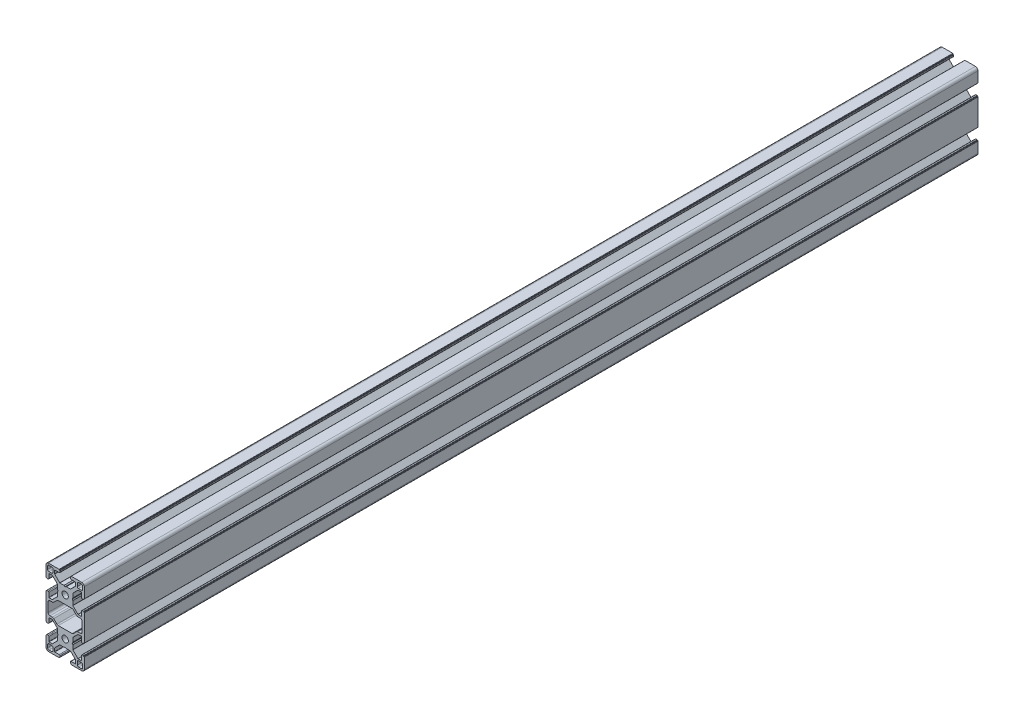
SolidWorks part; units mm, degrees
material "1060 Alloy"
ref_plane "Front" through (0, 0, 0) normal (0, 0, 1) x (1, 0, 0)
ref_plane "Top" through (0, 0, 0) normal (0, 1, 0) x (1, 0, 0)
ref_plane "Right" through (0, 0, 0) normal (1, 0, 0) x (0, 0, -1)
ref_plane "Plane1" through (0, 0, 25) normal (0, 0, 1) x (1, 0, 0)
sketch "Sketch1" plane through (0, 0, 25) normal (0, 0, 1) x (1, 0, 0)
  line L0 (-9.5, 12.7) -> (-9.5, 10.5)
  line L1 (-10.5, 9.5) -> (-12.7, 9.5)
  line L2 (-13.7, 10.5) -> (-13.7, 12.7)
  line L3 (-12.7, 13.7) -> (-10.5, 13.7)
  line L4 (12.7, 9.5) -> (10.5, 9.5)
  line L5 (9.5, 10.5) -> (9.5, 12.7)
  line L6 (10.5, 13.7) -> (12.7, 13.7)
  line L7 (13.7, 12.7) -> (13.7, 10.5)
  line L8 (-12.7, -39.5) -> (-10.5, -39.5)
  line L9 (-9.5, -40.5) -> (-9.5, -42.7)
  line L10 (-10.5, -43.7) -> (-12.7, -43.7)
  line L11 (-13.7, -42.7) -> (-13.7, -40.5)
  line L12 (9.5, -42.7) -> (9.5, -40.5)
  line L13 (10.5, -39.5) -> (12.7, -39.5)
  line L14 (13.7, -40.5) -> (13.7, -42.7)
  line L15 (12.7, -43.7) -> (10.5, -43.7)
  line L16 (0, 0) -> (0, -30) construction
  line L32 (8.9272, -20.5393) -> (6.4104, -23.0562)
  line L33 (5.3497, -23.4955) -> (-5.3497, -23.4955)
  line L34 (-6.4104, -23.0562) -> (-8.9272, -20.5393)
  line L35 (-9.9879, -20.1) -> (-11.85, -20.1)
  line L36 (-13.35, -18.6) -> (-13.35, -11.4)
  line L37 (-11.85, -9.9) -> (-9.9879, -9.9)
  line L38 (-8.9272, -9.4607) -> (-6.4104, -6.9438)
  line L39 (-5.3497, -6.5045) -> (5.3497, -6.5045)
  line L40 (6.4104, -6.9438) -> (8.9272, -9.4607)
  line L41 (9.9879, -9.9) -> (11.85, -9.9)
  line L42 (13.35, -11.4) -> (13.35, -18.6)
  line L43 (11.85, -20.1) -> (9.9879, -20.1)
  line L44 (13.4, -25.95) -> (14.3, -25.95)
  line L45 (14.5, -25.75) -> (14.5, -25.65)
  line L46 (14.7, -25.45) -> (14.8, -25.45)
  line L47 (15, -25.25) -> (15, -4.75)
  line L48 (14.8, -4.55) -> (14.7, -4.55)
  line L49 (14.5, -4.35) -> (14.5, -4.25)
  line L50 (14.3, -4.05) -> (13.4, -4.05)
  line L51 (12.8, -4.65) -> (12.8, -8.05)
  line L52 (12.6, -8.25) -> (10.1328, -8.25)
  line L53 (9.9914, -8.1914) -> (6.063, -4.263)
  line L54 (6.0045, -4.1216) -> (6.0045, -0.9)
  line L55 (6.0045, -0.9) -> (5.5426, -0.1)
  line L56 (5.5426, 0.1) -> (6.0045, 0.9)
  line L57 (6.0045, 0.9) -> (6.0045, 4.1216)
  line L58 (6.063, 4.263) -> (9.9914, 8.1914)
  line L59 (10.1328, 8.25) -> (12.6, 8.25)
  line L60 (12.8, 8.05) -> (12.8, 4.65)
  line L61 (13.4, 4.05) -> (14.3, 4.05)
  line L62 (14.5, 4.25) -> (14.5, 4.35)
  line L63 (14.7, 4.55) -> (14.8, 4.55)
  line L64 (15, 4.75) -> (15, 13)
  line L65 (13, 15) -> (4.75, 15)
  line L66 (4.55, 14.8) -> (4.55, 14.7)
  line L67 (4.35, 14.5) -> (4.25, 14.5)
  line L68 (4.05, 14.3) -> (4.05, 13.4)
  line L69 (4.65, 12.8) -> (8.05, 12.8)
  line L70 (8.25, 12.6) -> (8.25, 10.1328)
  line L71 (8.1914, 9.9914) -> (4.2586, 6.0586)
  line L72 (4.1172, 6) -> (0.9, 6)
  line L73 (0.9, 6) -> (0.1019, 5.5392)
  line L74 (-0.1019, 5.5392) -> (-0.9, 6)
  line L75 (-0.9, 6) -> (-4.1172, 6)
  line L76 (-4.2586, 6.0586) -> (-8.1914, 9.9914)
  line L77 (-8.25, 10.1328) -> (-8.25, 12.6)
  line L78 (-8.05, 12.8) -> (-4.65, 12.8)
  line L79 (-4.05, 13.4) -> (-4.05, 14.3)
  line L80 (-4.25, 14.5) -> (-4.35, 14.5)
  line L81 (-4.55, 14.7) -> (-4.55, 14.8)
  line L82 (-4.75, 15) -> (-13, 15)
  line L83 (-15, 13) -> (-15, 4.75)
  line L84 (-14.8, 4.55) -> (-14.7, 4.55)
  line L85 (-14.5, 4.35) -> (-14.5, 4.25)
  line L86 (-14.3, 4.05) -> (-13.4, 4.05)
  line L87 (-12.8, 4.65) -> (-12.8, 8.05)
  line L88 (-12.6, 8.25) -> (-10.1328, 8.25)
  line L89 (-9.9914, 8.1914) -> (-6.063, 4.263)
  line L90 (-6.0045, 4.1216) -> (-6.0045, 0.9)
  line L91 (-6.0045, 0.9) -> (-5.5426, 0.1)
  line L92 (-5.5426, -0.1) -> (-6.0045, -0.9)
  line L93 (-6.0045, -0.9) -> (-6.0045, -4.1216)
  line L94 (-6.063, -4.263) -> (-9.9914, -8.1914)
  line L95 (-10.1328, -8.25) -> (-12.6, -8.25)
  line L96 (-12.8, -8.05) -> (-12.8, -4.65)
  line L97 (-13.4, -4.05) -> (-14.3, -4.05)
  line L98 (-14.5, -4.25) -> (-14.5, -4.35)
  line L99 (-14.7, -4.55) -> (-14.8, -4.55)
  line L100 (-15, -4.75) -> (-15, -25.25)
  line L101 (-14.8, -25.45) -> (-14.7, -25.45)
  line L102 (-14.5, -25.65) -> (-14.5, -25.75)
  line L103 (-14.3, -25.95) -> (-13.4, -25.95)
  line L104 (-12.8, -25.35) -> (-12.8, -21.95)
  line L105 (-12.6, -21.75) -> (-10.1328, -21.75)
  line L106 (-9.9914, -21.8086) -> (-6.063, -25.737)
  line L107 (-6.0045, -25.8784) -> (-6.0045, -29.1)
  line L108 (-6.0045, -29.1) -> (-5.5426, -29.9)
  line L109 (-5.5426, -30.1) -> (-6.0045, -30.9)
  line L110 (-6.0045, -30.9) -> (-6.0045, -34.1216)
  line L111 (-6.063, -34.263) -> (-9.9914, -38.1914)
  line L112 (-10.1328, -38.25) -> (-12.6, -38.25)
  line L113 (-12.8, -38.05) -> (-12.8, -34.65)
  line L114 (-13.4, -34.05) -> (-14.3, -34.05)
  line L115 (-14.5, -34.25) -> (-14.5, -34.35)
  line L116 (-14.7, -34.55) -> (-14.8, -34.55)
  line L117 (-15, -34.75) -> (-15, -43)
  line L118 (-13, -45) -> (-4.75, -45)
  line L119 (-4.55, -44.8) -> (-4.55, -44.7)
  line L120 (-4.35, -44.5) -> (-4.25, -44.5)
  line L121 (-4.05, -44.3) -> (-4.05, -43.4)
  line L122 (-4.65, -42.8) -> (-8.05, -42.8)
  line L123 (-8.25, -42.6) -> (-8.25, -40.1328)
  line L124 (-8.1914, -39.9914) -> (-4.2586, -36.0586)
  line L125 (-4.1172, -36) -> (-0.9, -36)
  line L126 (-0.9, -36) -> (-0.1019, -35.5392)
  line L127 (0.1019, -35.5392) -> (0.9, -36)
  line L128 (0.9, -36) -> (4.1172, -36)
  line L129 (4.2586, -36.0586) -> (8.1914, -39.9914)
  line L130 (8.25, -40.1328) -> (8.25, -42.6)
  line L131 (8.05, -42.8) -> (4.65, -42.8)
  line L132 (4.05, -43.4) -> (4.05, -44.3)
  line L133 (4.25, -44.5) -> (4.35, -44.5)
  line L134 (4.55, -44.7) -> (4.55, -44.8)
  line L135 (4.75, -45) -> (13, -45)
  line L136 (15, -43) -> (15, -34.75)
  line L137 (14.8, -34.55) -> (14.7, -34.55)
  line L138 (14.5, -34.35) -> (14.5, -34.25)
  line L139 (14.3, -34.05) -> (13.4, -34.05)
  line L140 (12.8, -34.65) -> (12.8, -38.05)
  line L141 (12.6, -38.25) -> (10.1328, -38.25)
  line L142 (9.9914, -38.1914) -> (6.063, -34.263)
  line L143 (6.0045, -34.1216) -> (6.0045, -30.9)
  line L144 (6.0045, -30.9) -> (5.5426, -30.1)
  line L145 (5.5426, -29.9) -> (6.0045, -29.1)
  line L146 (6.0045, -29.1) -> (6.0045, -25.8784)
  line L147 (6.063, -25.737) -> (9.9914, -21.8086)
  line L148 (10.1328, -21.75) -> (12.6, -21.75)
  line L149 (12.8, -21.95) -> (12.8, -25.35)
  arc A0 (-9.5, 10.5) -> (-10.5, 9.5) centre (-10.5, 10.5) cw
  arc A1 (-12.7, 9.5) -> (-13.7, 10.5) centre (-12.7, 10.5) cw
  arc A2 (-13.7, 12.7) -> (-12.7, 13.7) centre (-12.7, 12.7) cw
  arc A3 (-10.5, 13.7) -> (-9.5, 12.7) centre (-10.5, 12.7) cw
  arc A4 (10.5, 9.5) -> (9.5, 10.5) centre (10.5, 10.5) cw
  arc A5 (9.5, 12.7) -> (10.5, 13.7) centre (10.5, 12.7) cw
  arc A6 (12.7, 13.7) -> (13.7, 12.7) centre (12.7, 12.7) cw
  arc A7 (13.7, 10.5) -> (12.7, 9.5) centre (12.7, 10.5) cw
  arc A8 (-10.5, -39.5) -> (-9.5, -40.5) centre (-10.5, -40.5) cw
  arc A9 (-9.5, -42.7) -> (-10.5, -43.7) centre (-10.5, -42.7) cw
  arc A10 (-12.7, -43.7) -> (-13.7, -42.7) centre (-12.7, -42.7) cw
  arc A11 (-13.7, -40.5) -> (-12.7, -39.5) centre (-12.7, -40.5) cw
  arc A12 (9.5, -40.5) -> (10.5, -39.5) centre (10.5, -40.5) cw
  arc A13 (12.7, -39.5) -> (13.7, -40.5) centre (12.7, -40.5) cw
  arc A14 (13.7, -42.7) -> (12.7, -43.7) centre (12.7, -42.7) cw
  arc A15 (10.5, -43.7) -> (9.5, -42.7) centre (10.5, -42.7) cw
  circle A16 centre (0, 0) radius 2.45
  circle A17 centre (0, -30) radius 2.45
  arc A32 (6.4104, -23.0562) -> (5.3497, -23.4955) centre (5.3497, -21.9955) cw
  arc A33 (-5.3497, -23.4955) -> (-6.4104, -23.0562) centre (-5.3497, -21.9955) cw
  arc A34 (-8.9272, -20.5393) -> (-9.9879, -20.1) centre (-9.9879, -21.6) ccw
  arc A35 (-11.85, -20.1) -> (-13.35, -18.6) centre (-11.85, -18.6) cw
  arc A36 (-13.35, -11.4) -> (-11.85, -9.9) centre (-11.85, -11.4) cw
  arc A37 (-9.9879, -9.9) -> (-8.9272, -9.4607) centre (-9.9879, -8.4) ccw
  arc A38 (-6.4104, -6.9438) -> (-5.3497, -6.5045) centre (-5.3497, -8.0045) cw
  arc A39 (5.3497, -6.5045) -> (6.4104, -6.9438) centre (5.3497, -8.0045) cw
  arc A40 (8.9272, -9.4607) -> (9.9879, -9.9) centre (9.9879, -8.4) ccw
  arc A41 (11.85, -9.9) -> (13.35, -11.4) centre (11.85, -11.4) cw
  arc A42 (13.35, -18.6) -> (11.85, -20.1) centre (11.85, -18.6) cw
  arc A43 (9.9879, -20.1) -> (8.9272, -20.5393) centre (9.9879, -21.6) ccw
  arc A44 (12.8, -25.35) -> (13.4, -25.95) centre (13.4, -25.35) ccw
  arc A45 (14.3, -25.95) -> (14.5, -25.75) centre (14.3, -25.75) ccw
  arc A46 (14.5, -25.65) -> (14.7, -25.45) centre (14.7, -25.65) cw
  arc A47 (14.8, -25.45) -> (15, -25.25) centre (14.8, -25.25) ccw
  arc A48 (15, -4.75) -> (14.8, -4.55) centre (14.8, -4.75) ccw
  arc A49 (14.7, -4.55) -> (14.5, -4.35) centre (14.7, -4.35) cw
  arc A50 (14.5, -4.25) -> (14.3, -4.05) centre (14.3, -4.25) ccw
  arc A51 (13.4, -4.05) -> (12.8, -4.65) centre (13.4, -4.65) ccw
  arc A52 (12.8, -8.05) -> (12.6, -8.25) centre (12.6, -8.05) cw
  arc A53 (10.1328, -8.25) -> (9.9914, -8.1914) centre (10.1328, -8.05) cw
  arc A54 (6.063, -4.263) -> (6.0045, -4.1216) centre (6.2045, -4.1216) cw
  arc A55 (5.5426, -0.1) -> (5.5426, 0.1) centre (5.7158, 0) cw
  arc A56 (6.0045, 4.1216) -> (6.063, 4.263) centre (6.2045, 4.1216) cw
  arc A57 (9.9914, 8.1914) -> (10.1328, 8.25) centre (10.1328, 8.05) cw
  arc A58 (12.6, 8.25) -> (12.8, 8.05) centre (12.6, 8.05) cw
  arc A59 (12.8, 4.65) -> (13.4, 4.05) centre (13.4, 4.65) ccw
  arc A60 (14.3, 4.05) -> (14.5, 4.25) centre (14.3, 4.25) ccw
  arc A61 (14.5, 4.35) -> (14.7, 4.55) centre (14.7, 4.35) cw
  arc A62 (14.8, 4.55) -> (15, 4.75) centre (14.8, 4.75) ccw
  arc A63 (15, 13) -> (13, 15) centre (13, 13) ccw
  arc A64 (4.75, 15) -> (4.55, 14.8) centre (4.75, 14.8) ccw
  arc A65 (4.55, 14.7) -> (4.35, 14.5) centre (4.35, 14.7) cw
  arc A66 (4.25, 14.5) -> (4.05, 14.3) centre (4.25, 14.3) ccw
  arc A67 (4.05, 13.4) -> (4.65, 12.8) centre (4.65, 13.4) ccw
  arc A68 (8.05, 12.8) -> (8.25, 12.6) centre (8.05, 12.6) cw
  arc A69 (8.25, 10.1328) -> (8.1914, 9.9914) centre (8.05, 10.1328) cw
  arc A70 (4.2586, 6.0586) -> (4.1172, 6) centre (4.1172, 6.2) cw
  arc A71 (0.1019, 5.5392) -> (-0.1019, 5.5392) centre (0, 5.7158) cw
  arc A72 (-4.1172, 6) -> (-4.2586, 6.0586) centre (-4.1172, 6.2) cw
  arc A73 (-8.1914, 9.9914) -> (-8.25, 10.1328) centre (-8.05, 10.1328) cw
  arc A74 (-8.25, 12.6) -> (-8.05, 12.8) centre (-8.05, 12.6) cw
  arc A75 (-4.65, 12.8) -> (-4.05, 13.4) centre (-4.65, 13.4) ccw
  arc A76 (-4.05, 14.3) -> (-4.25, 14.5) centre (-4.25, 14.3) ccw
  arc A77 (-4.35, 14.5) -> (-4.55, 14.7) centre (-4.35, 14.7) cw
  arc A78 (-4.55, 14.8) -> (-4.75, 15) centre (-4.75, 14.8) ccw
  arc A79 (-13, 15) -> (-15, 13) centre (-13, 13) ccw
  arc A80 (-15, 4.75) -> (-14.8, 4.55) centre (-14.8, 4.75) ccw
  arc A81 (-14.7, 4.55) -> (-14.5, 4.35) centre (-14.7, 4.35) cw
  arc A82 (-14.5, 4.25) -> (-14.3, 4.05) centre (-14.3, 4.25) ccw
  arc A83 (-13.4, 4.05) -> (-12.8, 4.65) centre (-13.4, 4.65) ccw
  arc A84 (-12.8, 8.05) -> (-12.6, 8.25) centre (-12.6, 8.05) cw
  arc A85 (-10.1328, 8.25) -> (-9.9914, 8.1914) centre (-10.1328, 8.05) cw
  arc A86 (-6.063, 4.263) -> (-6.0045, 4.1216) centre (-6.2045, 4.1216) cw
  arc A87 (-5.5426, 0.1) -> (-5.5426, -0.1) centre (-5.7158, 0) cw
  arc A88 (-6.0045, -4.1216) -> (-6.063, -4.263) centre (-6.2045, -4.1216) cw
  arc A89 (-9.9914, -8.1914) -> (-10.1328, -8.25) centre (-10.1328, -8.05) cw
  arc A90 (-12.6, -8.25) -> (-12.8, -8.05) centre (-12.6, -8.05) cw
  arc A91 (-12.8, -4.65) -> (-13.4, -4.05) centre (-13.4, -4.65) ccw
  arc A92 (-14.3, -4.05) -> (-14.5, -4.25) centre (-14.3, -4.25) ccw
  arc A93 (-14.5, -4.35) -> (-14.7, -4.55) centre (-14.7, -4.35) cw
  arc A94 (-14.8, -4.55) -> (-15, -4.75) centre (-14.8, -4.75) ccw
  arc A95 (-15, -25.25) -> (-14.8, -25.45) centre (-14.8, -25.25) ccw
  arc A96 (-14.7, -25.45) -> (-14.5, -25.65) centre (-14.7, -25.65) cw
  arc A97 (-14.5, -25.75) -> (-14.3, -25.95) centre (-14.3, -25.75) ccw
  arc A98 (-13.4, -25.95) -> (-12.8, -25.35) centre (-13.4, -25.35) ccw
  arc A99 (-12.8, -21.95) -> (-12.6, -21.75) centre (-12.6, -21.95) cw
  arc A100 (-10.1328, -21.75) -> (-9.9914, -21.8086) centre (-10.1328, -21.95) cw
  arc A101 (-6.063, -25.737) -> (-6.0045, -25.8784) centre (-6.2045, -25.8784) cw
  arc A102 (-5.5426, -29.9) -> (-5.5426, -30.1) centre (-5.7158, -30) cw
  arc A103 (-6.0045, -34.1216) -> (-6.063, -34.263) centre (-6.2045, -34.1216) cw
  arc A104 (-9.9914, -38.1914) -> (-10.1328, -38.25) centre (-10.1328, -38.05) cw
  arc A105 (-12.6, -38.25) -> (-12.8, -38.05) centre (-12.6, -38.05) cw
  arc A106 (-12.8, -34.65) -> (-13.4, -34.05) centre (-13.4, -34.65) ccw
  arc A107 (-14.3, -34.05) -> (-14.5, -34.25) centre (-14.3, -34.25) ccw
  arc A108 (-14.5, -34.35) -> (-14.7, -34.55) centre (-14.7, -34.35) cw
  arc A109 (-14.8, -34.55) -> (-15, -34.75) centre (-14.8, -34.75) ccw
  arc A110 (-15, -43) -> (-13, -45) centre (-13, -43) ccw
  arc A111 (-4.75, -45) -> (-4.55, -44.8) centre (-4.75, -44.8) ccw
  arc A112 (-4.55, -44.7) -> (-4.35, -44.5) centre (-4.35, -44.7) cw
  arc A113 (-4.25, -44.5) -> (-4.05, -44.3) centre (-4.25, -44.3) ccw
  arc A114 (-4.05, -43.4) -> (-4.65, -42.8) centre (-4.65, -43.4) ccw
  arc A115 (-8.05, -42.8) -> (-8.25, -42.6) centre (-8.05, -42.6) cw
  arc A116 (-8.25, -40.1328) -> (-8.1914, -39.9914) centre (-8.05, -40.1328) cw
  arc A117 (-4.2586, -36.0586) -> (-4.1172, -36) centre (-4.1172, -36.2) cw
  arc A118 (-0.1019, -35.5392) -> (0.1019, -35.5392) centre (0, -35.7158) cw
  arc A119 (4.1172, -36) -> (4.2586, -36.0586) centre (4.1172, -36.2) cw
  arc A120 (8.1914, -39.9914) -> (8.25, -40.1328) centre (8.05, -40.1328) cw
  arc A121 (8.25, -42.6) -> (8.05, -42.8) centre (8.05, -42.6) cw
  arc A122 (4.65, -42.8) -> (4.05, -43.4) centre (4.65, -43.4) ccw
  arc A123 (4.05, -44.3) -> (4.25, -44.5) centre (4.25, -44.3) ccw
  arc A124 (4.35, -44.5) -> (4.55, -44.7) centre (4.35, -44.7) cw
  arc A125 (4.55, -44.8) -> (4.75, -45) centre (4.75, -44.8) ccw
  arc A126 (13, -45) -> (15, -43) centre (13, -43) ccw
  arc A127 (15, -34.75) -> (14.8, -34.55) centre (14.8, -34.75) ccw
  arc A128 (14.7, -34.55) -> (14.5, -34.35) centre (14.7, -34.35) cw
  arc A129 (14.5, -34.25) -> (14.3, -34.05) centre (14.3, -34.25) ccw
  arc A130 (13.4, -34.05) -> (12.8, -34.65) centre (13.4, -34.65) ccw
  arc A131 (12.8, -38.05) -> (12.6, -38.25) centre (12.6, -38.05) cw
  arc A132 (10.1328, -38.25) -> (9.9914, -38.1914) centre (10.1328, -38.05) cw
  arc A133 (6.063, -34.263) -> (6.0045, -34.1216) centre (6.2045, -34.1216) cw
  arc A134 (5.5426, -30.1) -> (5.5426, -29.9) centre (5.7158, -30) cw
  arc A135 (6.0045, -25.8784) -> (6.063, -25.737) centre (6.2045, -25.8784) cw
  arc A136 (9.9914, -21.8086) -> (10.1328, -21.75) centre (10.1328, -21.95) cw
  arc A137 (12.6, -21.75) -> (12.8, -21.95) centre (12.6, -21.95) cw
  dimension "D1" = 4.9
  dimension "D3" = 4.9
  dimension "D2" = 30
extrude "Boss-Extrude1" add sketch "Sketch1" against normal blind 700
sketch "Sketch2" plane through (15, 0, 0) normal (1, 0, 0) x (0, 0, -1)
  line L0 (20, 15) -> (20, -45) construction
  line L1 (675, 15) -> (-25, 15) construction
  line L2 (675, -45) -> (-25, -45) construction
  line L3 (-25, -25.25) -> (-25, -4.75) construction
  line L4 (660, 15) -> (660, -45) construction
  line L5 (675, -25.25) -> (675, -4.75) construction
  circle A0 centre (20, 0) radius 3
  circle A1 centre (20, -30) radius 3
  circle A2 centre (660, 0) radius 3
  circle A3 centre (660, -30) radius 3
  point P20 (675, -15)
  dimension "D2" = 6
  dimension "D3" = 6
  dimension "D4" = 15
  dimension "D5" = 30
  dimension "D7" = 15
  dimension "D8" = 30
  dimension "D9" = 6
  dimension "D10" = 6
  dimension "D1" = 45
  dimension "D6" = 15
extrude "Cut-Extrude1" cut sketch "Sketch2" against normal through all
sketch "Sketch3" plane through (0, -45, 0) normal (0, -1, 0) x (1, 0, 0)
  line L0 (-15, -20) -> (15, -20) construction
  line L1 (-15, -675) -> (-15, 25) construction
  line L2 (15, -675) -> (15, 25) construction
  line L3 (-13, 25) -> (-4.75, 25) construction
  line L4 (-15, -660) -> (15, -660) construction
  line L5 (-13, -675) -> (-4.75, -675) construction
  circle A0 centre (0, -20) radius 3
  circle A1 centre (0, -660) radius 3
  dimension "D2" = 6
  dimension "D4" = 6
  dimension "D1" = 45
  dimension "D3" = 15
extrude "Cut-Extrude2" cut sketch "Sketch3" against normal through all
hole_wizard "M6x1.0 Tapped Hole1" positions "Sketch4" profile "Sketch5" tap size "M6x1.0" standard "ANSI Metric"
sketch "Sketch4" plane through (0, 0, 25) normal (0, 0, 1) x (1, 0, 0)
  point P0 (0, 0)
  point P3 (0, -30)
sketch "Sketch5" plane through (0, 0, 25) normal (1, 0, 0) x (0, -1, 0)
  line L0 (0, 0) -> (0, 29.5022)
  line L1 (0, 29.5022) -> (2.5, 28)
  line L2 (2.5, 28) -> (2.5, 0)
  line L5 (2.5, 0) -> (0, 0)
  line L10 (0, 29.5022) -> (-2.5, 28) construction
  line L11 (0, -6.35) -> (0, 107.95) construction
  dimension "Tap Drill Dia." = 5
  dimension "Tap Drill Depth" = 28
  dimension "Drill Angle" = 118
cosmetic thread "Hole Thread1" parameters "D1"=25, "D2"=6
cosmetic thread "Hole Thread2" parameters "D1"=25, "D2"=6
hole_wizard "M6x1.0 Tapped Hole2" positions "Sketch6" profile "Sketch7" tap size "M6x1.0" standard "ANSI Metric"
sketch "Sketch6" plane through (0, 0, -675) normal (0, 0, -1) x (-1, 0, 0)
  point P0 (0, 0)
  point P3 (0, -30)
sketch "Sketch7" plane through (0, 0, -675) normal (1, 0, 0) x (0, 1, 0)
  line L0 (0, 0) -> (0, 29.5022)
  line L1 (0, 29.5022) -> (2.5, 28)
  line L2 (2.5, 28) -> (2.5, 0)
  line L5 (2.5, 0) -> (0, 0)
  line L10 (0, 29.5022) -> (-2.5, 28) construction
  line L11 (0, -6.35) -> (0, 107.95) construction
  dimension "Tap Drill Dia." = 5
  dimension "Tap Drill Depth" = 28
  dimension "Drill Angle" = 118
cosmetic thread "Hole Thread3" parameters "D1"=25, "D2"=6
cosmetic thread "Hole Thread4" parameters "D1"=25, "D2"=6
